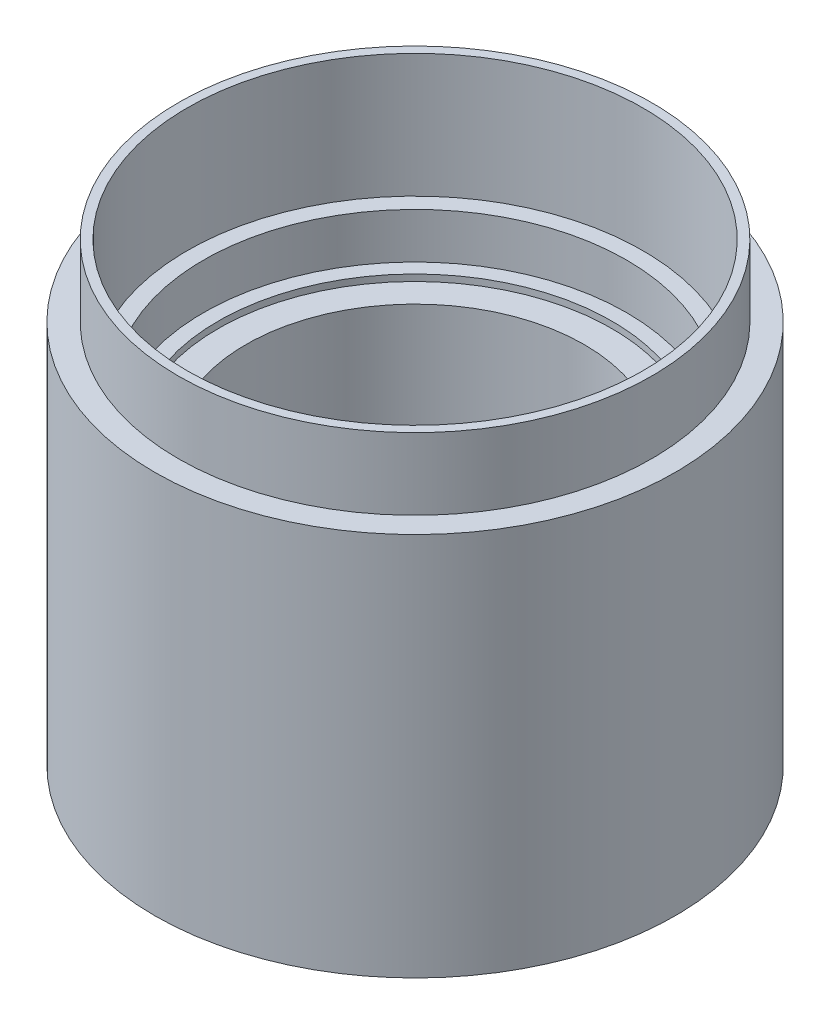
SolidWorks part; units mm, degrees
ref_plane "Front Plane" through (0, 0, 0) normal (0, 0, 1) x (1, 0, 0)
ref_plane "Top Plane" through (0, 0, 0) normal (0, 1, 0) x (1, 0, 0)
ref_plane "Right Plane" through (0, 0, 0) normal (1, 0, 0) x (0, 0, -1)
sketch "Sketch1" plane through (0, 0, 0) normal (0, 1, 0) x (1, 0, 0)
  line L1 (-50, 40) -> (50, 40)
  line L2 (-50, 40) -> (-50, -40)
  line L3 (-50, -40) -> (50, -40)
  line L4 (50, 40) -> (50, -40)
  line L5 (-50, 40) -> (50, -40) construction
  line L6 (-50, -40) -> (50, 40) construction
  circle A1 centre (0, 0) radius 26
  circle A2 centre (0, 0) radius 40
  point P0 (0, 0)
  dimension "D3" = 52
  dimension "D1" = 80
  dimension "D2" = 100
extrude "Boss-Extrude1" add sketch "Sketch1" along normal blind 70 contours A2 A1 region at (27.4843, 0, -27.4843)
sketch "Sketch2" plane through (0, 70, 0) normal (0, 1, 0) x (1, 0, 0)
  circle A0 centre (0, 0) radius 32.5
  dimension "D1" = 65
extrude "Cut-Extrude1" cut sketch "Sketch2" against normal blind 27
sketch "Sketch4" plane through (0, 43, 0) normal (0, 1, 0) x (1, 0, 0)
  circle A0 centre (0, 0) radius 30.25
  circle M3 centre (0, 0) radius 32.5
  dimension "D1" = 60.5
extrude "Boss-Extrude2" add sketch "Sketch4" along normal blind 1 contours A0 M3 region at (-31.5808, 43, 0)
sketch "Sketch5" plane through (0, 70, 0) normal (0, 1, 0) x (1, 0, 0)
  circle A0 centre (0, 0) radius 35
  dimension "D1" = 70
extrude "Cut-Extrude2" cut sketch "Sketch5" against normal offset from surface (19 mm away) 7 up to face at (0, 44, 30.25)
sketch "Sketch6" plane through (0, 0, 0) normal (0, -1, 0) x (1, 0, 0)
  circle A0 centre (0, 0) radius 32.5
  dimension "D1" = 65
extrude "Cut-Extrude3" cut sketch "Sketch6" against normal blind 8
sketch "Sketch7" plane through (0, 8, 0) normal (0, -1, 0) x (1, 0, 0)
  circle A0 centre (0, 0) radius 30.25
  dimension "D1" = 60.5
extrude "Cut-Extrude4" cut sketch "Sketch7" against normal blind 1
sketch "Sketch8" plane through (0, 70, 0) normal (0, 1, 0) x (1, 0, 0)
  circle A0 centre (0, 0) radius 36.3781
  circle A1 centre (0, 0) radius 41.8812
extrude "Schnitt-Linear austragen1" cut sketch "Sketch8" against normal blind 11
